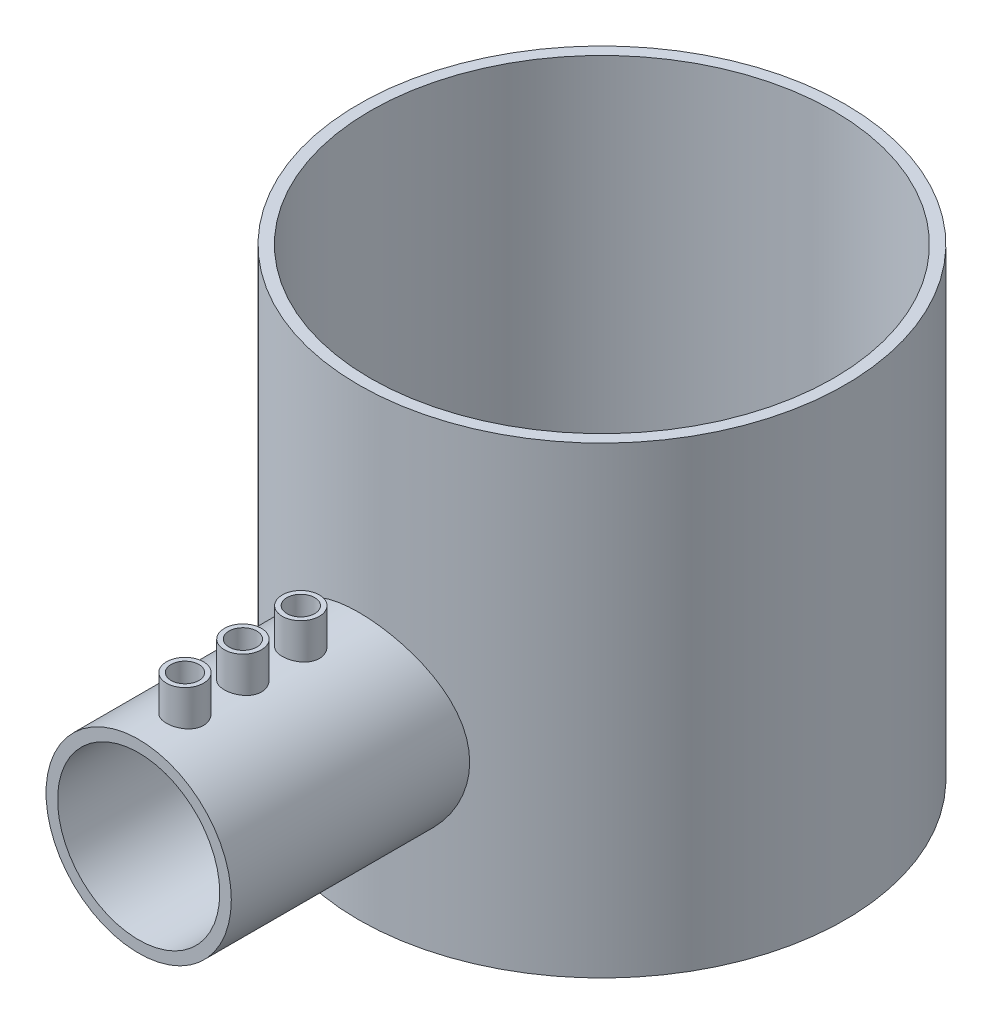
SolidWorks part; units mm, degrees
ref_plane "Front Plane" through (0, 0, 0) normal (0, 0, 1) x (1, 0, 0)
ref_plane "Top Plane" through (0, 0, 0) normal (0, 1, 0) x (1, 0, 0)
ref_plane "Right Plane" through (0, 0, 0) normal (1, 0, 0) x (0, 0, -1)
sketch "Sketch1" plane through (0, 0, 0) normal (0, 1, 0) x (1, 0, 0)
  circle A0 centre (0, 0) radius 105
  circle A1 centre (0, 0) radius 100
  dimension "D1" = 210
  dimension "D2" = 200
extrude "Boss-Extrude1" add sketch "Sketch1" along normal blind 200
sketch "Sketch2" plane through (0, 0, 0) normal (0, 0, 1) x (1, 0, 0)
  line L0 (-105, 0) -> (105, 0) construction
  circle A0 centre (0, 75) radius 40
  circle A1 centre (0, 75) radius 35
  circle A2 centre (0, 75) radius 8
  circle A3 centre (0, 75) radius 6
  dimension "D1" = 80
  dimension "D4" = 16
  dimension "D3" = 75
  dimension "D2" = 5
  dimension "D5" = 2
extrude "Boss-Extrude2" add sketch "Sketch2" against normal up to surface (102.9176 mm away) from offset 200 contours A0 | A1 up to face at (0, 200, 105)
extrude "Cut-Extrude1" cut sketch "Sketch2<3>" along normal up to next contours A1
sketch "Sketch2<3>" plane through (0, 0, 0) normal (0, 0, 1) x (1, 0, 0) same geometry as "Sketch2"
sketch "Sketch3" plane through (0, 0, 0) normal (0, 1, 0) x (1, 0, 0)
  line L0 (-40, -200) -> (40, -200) construction
  line L1 (-40, -97.0825) -> (-40, -200) construction
  line L2 (40, -200) -> (40, -97.0824) construction
  line L3 (-40, -200) -> (40, -200)
  line L4 (-40, -97.0825) -> (-40, -200)
  line L5 (40, -200) -> (40, -97.0824)
  circle A0 centre (0, -180) radius 8
  circle A1 centre (0, -155) radius 8
  circle A2 centre (0, -130) radius 8
  circle A3 centre (0, -130) radius 6
  circle A4 centre (0, -155) radius 6
  circle A5 centre (0, -180) radius 6
  point P8 (0, -200)
  dimension "D1" = 16
  dimension "D2" = 16
  dimension "D6" = 16
  dimension "D3" = 20
  dimension "D4" = 25
  dimension "D5" = 25
  dimension "D7" = 2
extrude "Boss-Extrude3" add sketch "Sketch3" against normal up to surface (15 mm away) from offset 130 contours A2 A3 | A1 A4 | A0 A5 region at (-7.7737, 0, 180) region at (-7.7737, 0, 155) region at (-7.7737, 0, 130) up to face at (40, 75, 200)
extrude "Boss-Extrude4" add sketch "Sketch2<5>" along normal up to surface (15.3052 mm away) from offset 120 contours A2 A3 region at (-7.7737, 75, 0) up to face at (-39.5214, 68.8305, 97.2783) offset against normal yes
sketch "Sketch2<5>" plane through (0, 0, 0) normal (0, 0, 1) x (1, 0, 0) same geometry as "Sketch2"
